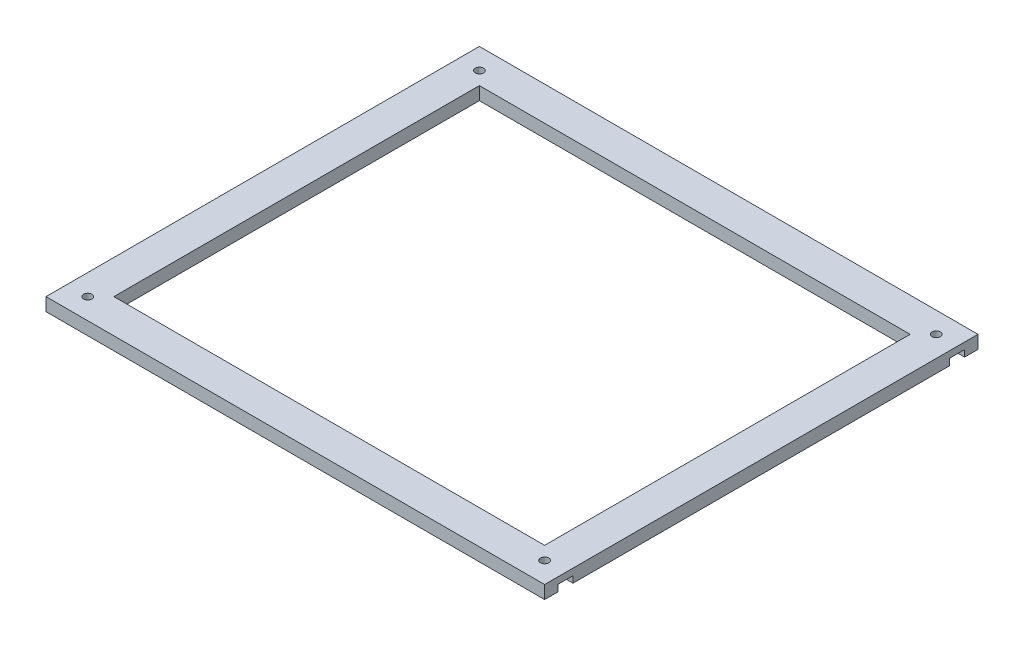
SolidWorks part; units mm, degrees
ref_plane "Front Plane" through (0, 0, 0) normal (0, 0, 1) x (1, 0, 0)
ref_plane "Top Plane" through (0, 0, 0) normal (0, 1, 0) x (1, 0, 0)
ref_plane "Right Plane" through (0, 0, 0) normal (1, 0, 0) x (0, 0, -1)
sketch "Sketch2" plane through (0, 0, 0) normal (0, 1, 0) x (1, 0, 0)
  line L0 (-92.5, 80) -> (-82.5, 70) construction
  line L1 (-92.5, -80) -> (92.5, -80)
  line L2 (-92.5, -80) -> (-92.5, 80)
  line L3 (-92.5, 80) -> (92.5, 80)
  line L4 (92.5, -80) -> (92.5, 80)
  line L5 (0, 80) -> (0, -80) construction
  line L6 (-92.5, 0) -> (92.5, 0) construction
  line L7 (-82.5, -70) -> (82.5, -70)
  line L8 (-82.5, -70) -> (-82.5, 70)
  line L9 (-82.5, 70) -> (82.5, 70)
  line L10 (82.5, -70) -> (82.5, 70)
  line L11 (0, 70) -> (0, -70) construction
  line L12 (-82.5, 0) -> (82.5, 0) construction
  line L13 (89.1454, 77.85) -> (90.7909, 75)
  line L14 (-90.7909, 75) -> (-89.1454, 72.15)
  line L15 (-89.1454, 72.15) -> (-85.8546, 72.15)
  line L16 (-85.8546, 72.15) -> (-84.2091, 75)
  line L17 (-84.2091, 75) -> (-85.8546, 77.85)
  line L18 (-85.8546, 77.85) -> (-89.1454, 77.85)
  line L19 (-89.1454, 77.85) -> (-90.7909, 75)
  line L20 (85.8546, 77.85) -> (89.1454, 77.85)
  line L21 (84.2091, 75) -> (85.8546, 77.85)
  line L22 (85.8546, 72.15) -> (84.2091, 75)
  line L23 (89.1454, 72.15) -> (85.8546, 72.15)
  line L24 (90.7909, 75) -> (89.1454, 72.15)
  line L25 (85.8546, -77.85) -> (89.1454, -77.85)
  line L26 (84.2091, -75) -> (85.8546, -77.85)
  line L27 (85.8546, -72.15) -> (84.2091, -75)
  line L28 (89.1454, -72.15) -> (85.8546, -72.15)
  line L29 (90.7909, -75) -> (89.1454, -72.15)
  line L30 (89.1454, -77.85) -> (90.7909, -75)
  line L31 (-89.1454, -77.85) -> (-90.7909, -75)
  line L32 (-85.8546, -77.85) -> (-89.1454, -77.85)
  line L33 (-84.2091, -75) -> (-85.8546, -77.85)
  line L34 (-85.8546, -72.15) -> (-84.2091, -75)
  line L35 (-89.1454, -72.15) -> (-85.8546, -72.15)
  line L36 (-90.7909, -75) -> (-89.1454, -72.15)
  line L37 (-89.1454, 77.85) -> (-92.5, 77.85)
  line L38 (-89.1454, 72.15) -> (-92.5, 72.15)
  line L39 (89.1454, 72.15) -> (92.5, 72.15)
  line L40 (89.1454, 77.85) -> (92.5, 77.85)
  line L41 (89.1454, -72.15) -> (95.5, -72.15)
  line L42 (89.1454, -77.85) -> (95.5, -77.85)
  line L43 (-85.8546, -72.15) -> (-95.5, -72.15)
  line L44 (-89.1454, -77.85) -> (-95.5, -77.85)
  line L45 (95.5, 83) -> (95.5, -83)
  line L46 (-95.5, 83) -> (-95.5, -83)
  line L47 (-95.5, -83) -> (95.5, -83)
  line L48 (95.5, -83) -> (95.5, 83)
  line L49 (-95.5, -83) -> (-95.5, 83)
  line L50 (89.1454, 77.85) -> (95.5, 77.85)
  line L51 (89.1454, 72.15) -> (95.5, 72.15)
  line L52 (-89.1454, 77.85) -> (-95.5, 77.85)
  line L53 (-85.8546, 72.15) -> (-95.5, 72.15)
  line L54 (-95.5, 83) -> (95.5, 83)
  circle A0 centre (-87.5, 75) radius 1.6
  circle A1 centre (87.5, 75) radius 1.6
  circle A2 centre (87.5, -75) radius 1.6
  circle A3 centre (-87.5, -75) radius 1.6
  circle A4 centre (-87.5, 75) radius 2.85 construction
  point P0 (0, 0)
  point P4 (0, 0)
  dimension "D5" = 3.2
  dimension "D1" = 160
  dimension "D2" = 185
  dimension "D3" = 10
  dimension "D4" = 10
  dimension "D6" = 5.7
  dimension "D7" = 3
  dimension "D8" = 3
  dimension "D9" = 3
  dimension "D10" = 90
extrude "Boss-Extrude1" add sketch "Sketch2" against normal blind 5 contours L1 L4 L3 L2 L30 L25 L26 L27 L28 L29 L19 L18 L17 L16 L15 L14 L10 L7 L8 L9 L13 L24 L23 L22 L21 L20 L31 L36 L35 L34 L33 L32 | L52 L2 L46 | L2 L53 L46 L43 | L47 L48 L42 L4 L1 L2 L44 L46 | L51 L4 L41 L48 region at (-90.0541, 0, 78.925) region at (0, 0, 81.4433) region at (-94, 0, 0) region at (94, 0, 0) region at (0, 0, -81.4433)
extrude "Boss-Extrude2" add sketch "Sketch2<3>" against normal blind 2.5 contours L18 L19 L14 L15 L16 L17 A0 | L36 L31 L32 L33 L34 L35 A3 | L25 L30 L29 L28 L27 L26 A2 | L24 L13 L20 L21 L22 L23 A1 | L40 L13 L24 L39 L4 | L30 L42 L4 L41 L29 | L44 L31 L36 L43 L2 | L38 L14 L19 L37 L2 | L53 L2 L52 L46 | L43 L46 L44 L2 | L42 L48 L41 L4 | L4 L51 L48 L50 region at (-94, 0, 75) region at (-91.1895, 0, 75) region at (91.1895, 0, 75) region at (94, 0, 75) region at (-89.8928, 0, 76.3815) region at (87.5, 0, 77.7629) region at (-94, 0, -75) region at (-91.1895, 0, -75) region at (91.1895, 0, -75) region at (94, 0, -75) region at (-89.8928, 0, -73.6185) region at (87.5, 0, -72.2371)
sketch "Sketch2<3>" plane through (0, 0, 0) normal (0, 1, 0) x (1, 0, 0) same geometry as "Sketch2"
